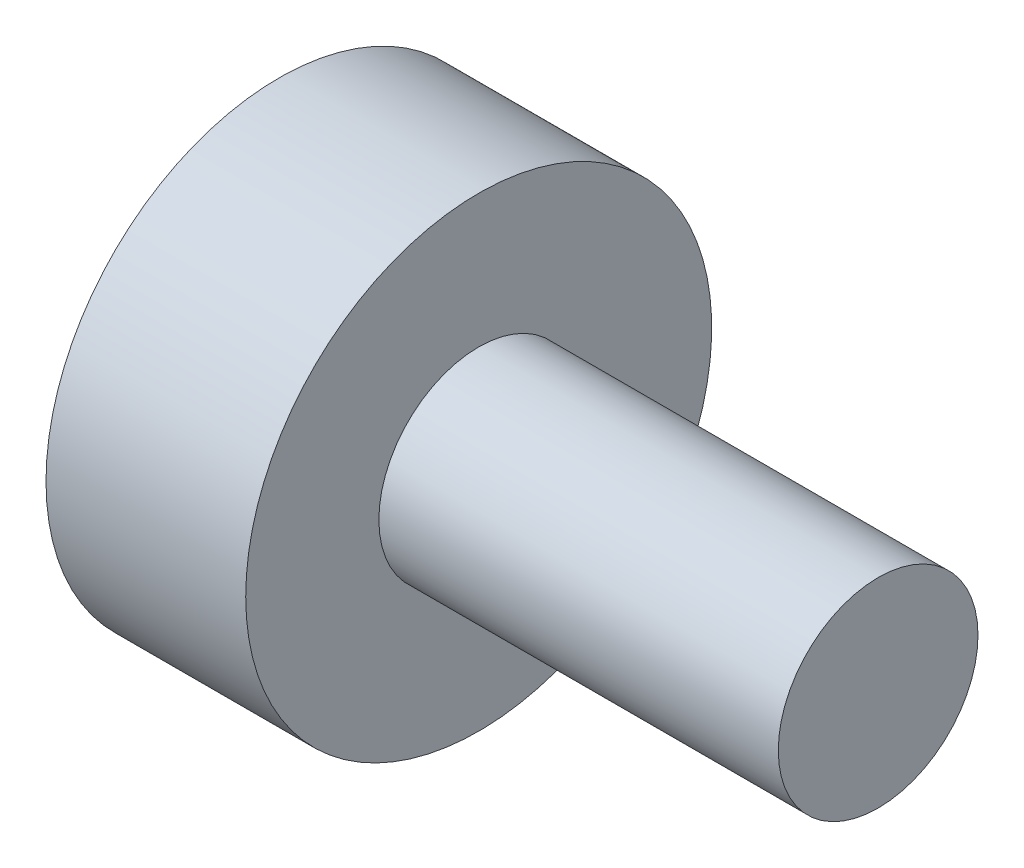
SolidWorks part; units mm, degrees
ref_plane "Спереди" through (0, 0, 0) normal (0, 0, 1) x (1, 0, 0)
ref_plane "Сверху" through (0, 0, 0) normal (0, 1, 0) x (1, 0, 0)
ref_plane "Справа" through (0, 0, 0) normal (1, 0, 0) x (0, 0, -1)
sketch "Эскиз1" plane through (0, 0, 0) normal (0, 0, 1) x (1, 0, 0)
  line L0 (0, 0) -> (100, 0)
  line L1 (0, 0) -> (0, 20)
  line L2 (0, 20) -> (10, 20)
  line L3 (10, 20) -> (10, 35)
  line L4 (10, 35) -> (40, 35)
  line L5 (40, 35) -> (40, 15)
  line L6 (40, 15) -> (100, 15)
  line L7 (100, 0) -> (100, 15)
revolve "Повернуть1" add sketch "Эскиз1" angle 360 about L0
sketch "Эскиз2" plane through (0, 0, 0) normal (1, 0, 0) x (0, 0, -1)
  circle A0 centre (0, 0) radius 4.25
extrude "Вырез-Вытянуть1" cut sketch "Эскиз2" along normal blind 20
thread "Резьба1" pitch 1.5 method cut profile "Профиль резьбы1" start angle 0, offset 0, length 20, pitch 1.5, diameter 8.5
ref_plane "Плоскость4" through (0, 0, -4.25) normal (0, -1, 0) x (0, 0, -1)
sketch "Профиль резьбы1" plane through (0, 0, -4.25) normal (0, -1, 0) x (0, 0, -1)
  line L0 (0, 0) -> (0, 1.5) construction
  line L1 (0, 0) -> (0.8119, 0.4687)
  line L2 (0.8119, 0.4687) -> (0.8119, 0.6562)
  line L3 (0.8119, 0.6562) -> (0, 1.125)
  line L4 (0.8119, 0.5625) -> (0, 0.5625) construction
  line L11 (0, 0) -> (0, 1.125)
  point P2 (0, 0)
  dimension "Pitch" = 1.5
  dimension "Profile_Angle" = 60
  dimension "Profile_Land" = 0.1875
  dimension "Profile_Height" = 0.8119
